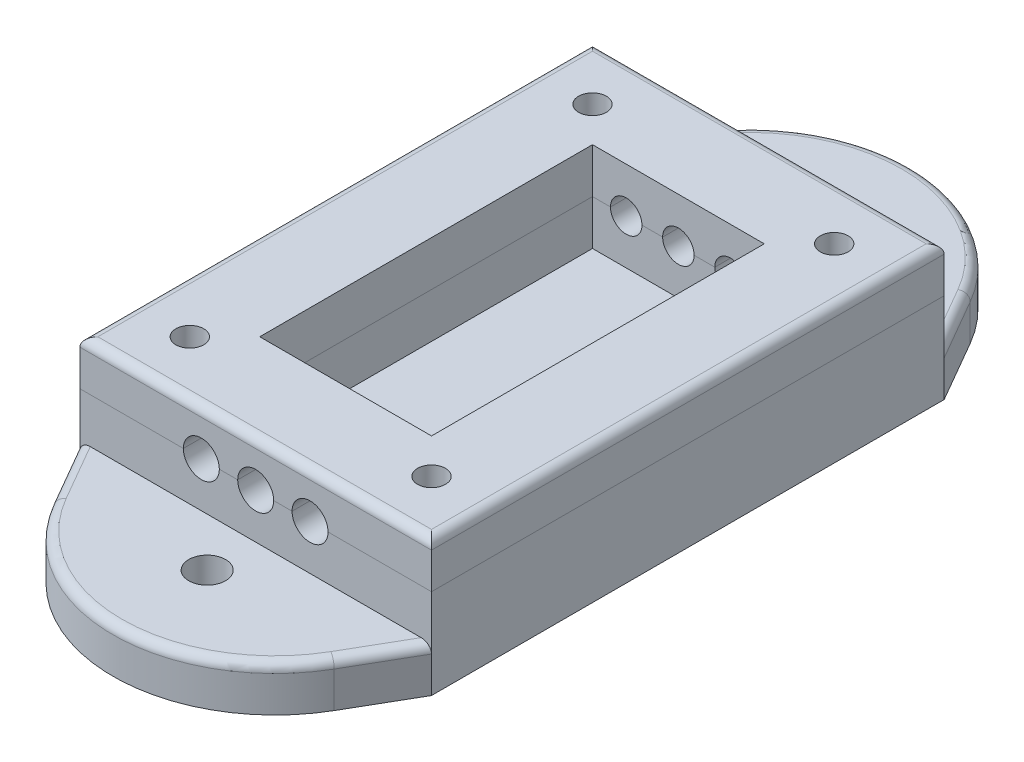
SolidWorks part; units mm, degrees
note: The reader was unsure of these and kept them because the rebuilt part matched: shared geometry of "Esquisse3<3>".
material "PLA"
ref_plane "Plan de face" through (0, 0, 0) normal (0, 0, 1) x (1, 0, 0)
ref_plane "Plan de dessus" through (0, 0, 0) normal (0, 1, 0) x (1, 0, 0)
ref_plane "Plan de droite" through (0, 0, 0) normal (1, 0, 0) x (0, 0, -1)
sketch "Esquisse1" plane through (0, 0, 0) normal (0, 0, 1) x (1, 0, 0)
  line L0 (0, 4) -> (0, 14.517) construction
  line L1 (-2.95, 10.1031) -> (2.95, 10.1031)
  line L22 (2.95, 10.1031) -> (2.95, 8.4831)
  line L23 (2.95, 8.4831) -> (5.71, 8.4831)
  line L24 (5.71, 8.4831) -> (5.71, 6.9831)
  line L25 (5.71, 6.9831) -> (3.5, 4.84)
  line L26 (3.5, 4.84) -> (-3.5, 4.84)
  line L27 (-5.71, 6.9831) -> (-3.5, 4.84)
  line L28 (-5.71, 8.4831) -> (-5.71, 6.9831)
  line L29 (-2.95, 8.4831) -> (-5.71, 8.4831)
  line L30 (-2.95, 10.1031) -> (-2.95, 8.4831)
  point P10 (0, 4.84)
  point P14 (0, 10.1031)
  point P41 (0, 0)
  point P46 (0, 0)
  line B0 (0, 0) -> (0, 4) construction
  line B1 (0, 4) -> (0.866, 4.5)
  line B2 (0, 4) -> (-0.866, 4.5)
  line B3 (0.866, 4.5) -> (3.4393, 4.5)
  line B4 (3.4393, 4.5) -> (6, 7.0607)
  line B5 (6, 7.0607) -> (6, 8.5)
  line B6 (6, 8.5) -> (3, 8.5)
  line B7 (3, 8.5) -> (3, 9.5)
  line B8 (3, 9.5) -> (3.5, 9.5)
  line B9 (3.5, 9.5) -> (3.5, 10)
  line B10 (3.5, 10) -> (8.5, 10)
  line B11 (0, 0) -> (1.2745, 0) construction
  line B12 (-3.5, -10) -> (-8.5, -10)
  line B13 (-3.4393, -4.5) -> (-6, -7.0607)
  line B14 (-3.5, 9.5) -> (-3.5, 10)
  line B15 (-3, 9.5) -> (-3.5, 9.5)
  line B16 (-3, 8.5) -> (-3, 9.5)
  line B17 (-6, 8.5) -> (-3, 8.5)
  line B18 (-6, 7.0607) -> (-6, 8.5)
  line B19 (-0.866, 4.5) -> (-3.4393, 4.5)
  line B20 (-3.4393, 4.5) -> (-6, 7.0607)
  line B21 (-3.5, 10) -> (-8.5, 10)
  line B22 (-0.866, -4.5) -> (-3.4393, -4.5)
  line B23 (-6, -7.0607) -> (-6, -8.5)
  line B24 (-6, -8.5) -> (-3, -8.5)
  line B25 (-3, -8.5) -> (-3, -9.5)
  line B26 (-3, -9.5) -> (-3.5, -9.5)
  line B27 (-3.5, -9.5) -> (-3.5, -10)
  line B28 (3.5, -10) -> (8.5, -10)
  line B29 (3.5, -9.5) -> (3.5, -10)
  line B30 (3, -9.5) -> (3.5, -9.5)
  line B31 (3, -8.5) -> (3, -9.5)
  line B32 (6, -8.5) -> (3, -8.5)
  line B33 (6, -7.0607) -> (6, -8.5)
  line B34 (3.4393, -4.5) -> (6, -7.0607)
  line B35 (0.866, -4.5) -> (3.4393, -4.5)
  line B36 (0, -4) -> (-0.866, -4.5)
  line B37 (0, -4) -> (0.866, -4.5)
  line B38 (10, -3.5) -> (10, -8.5)
  line B39 (9.5, -3.5) -> (10, -3.5)
  line B40 (8.5, -3) -> (9.5, -3)
  line B41 (9.5, -3) -> (9.5, -3.5)
  line B42 (8.5, -6) -> (8.5, -3)
  line B43 (7.0607, -6) -> (8.5, -6)
  line B44 (4.5, -3.4393) -> (7.0607, -6)
  line B45 (4.5, -0.866) -> (4.5, -3.4393)
  line B46 (4.5, 0.866) -> (4.5, 3.4393)
  line B47 (4.5, 3.4393) -> (7.0607, 6)
  line B48 (7.0607, 6) -> (8.5, 6)
  line B49 (8.5, 6) -> (8.5, 3)
  line B50 (8.5, 3) -> (9.5, 3)
  line B51 (9.5, 3) -> (9.5, 3.5)
  line B52 (9.5, 3.5) -> (10, 3.5)
  line B53 (10, 3.5) -> (10, 8.5)
  line B54 (-3.5, -9.5) -> (-3.5, -10)
  line B55 (-3, -8.5) -> (-3, -9.5)
  line B56 (-3, -9.5) -> (-3.5, -9.5)
  line B57 (-6, -8.5) -> (-3, -8.5)
  line B58 (-6, -7.0607) -> (-6, -8.5)
  line B59 (-3.4393, -4.5) -> (-6, -7.0607)
  line B60 (-0.866, -4.5) -> (-3.4393, -4.5)
  line B61 (0.866, -4.5) -> (3.4393, -4.5)
  line B62 (3.4393, -4.5) -> (6, -7.0607)
  line B63 (6, -7.0607) -> (6, -8.5)
  line B64 (6, -8.5) -> (3, -8.5)
  line B65 (3, -8.5) -> (3, -9.5)
  line B66 (3, -9.5) -> (3.5, -9.5)
  line B67 (3.5, -9.5) -> (3.5, -10)
  line B68 (-10, 3.5) -> (-10, 8.5)
  line B69 (-9.5, 3.5) -> (-10, 3.5)
  line B70 (-8.5, 3) -> (-9.5, 3)
  line B71 (-9.5, 3) -> (-9.5, 3.5)
  line B72 (-8.5, 6) -> (-8.5, 3)
  line B73 (-7.0607, 6) -> (-8.5, 6)
  line B74 (-4.5, 3.4393) -> (-7.0607, 6)
  line B75 (-4.5, 0.866) -> (-4.5, 3.4393)
  line B76 (-4.5, -0.866) -> (-4.5, -3.4393)
  line B77 (-4.5, -3.4393) -> (-7.0607, -6)
  line B78 (-7.0607, -6) -> (-8.5, -6)
  line B79 (-8.5, -6) -> (-8.5, -3)
  line B80 (-8.5, -3) -> (-9.5, -3)
  line B81 (-9.5, -3) -> (-9.5, -3.5)
  line B82 (-9.5, -3.5) -> (-10, -3.5)
  line B83 (-10, -3.5) -> (-10, -8.5)
  line B84 (4, 0) -> (4.5, -0.866)
  line B85 (4, 0) -> (4.5, 0.866)
  line B86 (0, -4) -> (-0.866, -4.5)
  line B87 (0, -4) -> (0.866, -4.5)
  line B88 (-4, 0) -> (-4.5, 0.866)
  line B89 (-4, 0) -> (-4.5, -0.866)
  line B90 (0, 0) -> (1.9445, 1.9445) construction
  arc B91 (8.5, 10) -> (10, 8.5) centre (8.5, 8.5) cw
  arc B92 (-8.5, 10) -> (-10, 8.5) centre (-8.5, 8.5) ccw
  arc B93 (-8.5, -10) -> (-10, -8.5) centre (-8.5, -8.5) cw
  arc B94 (8.5, -10) -> (10, -8.5) centre (8.5, -8.5) ccw
  circle B95 centre (0, 0) radius 2.75
  dimension "D1" = 2.95
  dimension "D2" = 1.62
  dimension "D3" = 2.76
  dimension "D4" = 1.5
  dimension "D5" = 135.88
  dimension "D6" = 3.5
  dimension "D7" = 0.34
sketch_block_instance "Bloc1-1"
sketch_block "Bloc1"
extrude "Boss.-Extru.1" add sketch "Esquisse1" against normal blind 20 contours L0 L26 L25 L24 L23 L22 L1 | L26 L0 L1 L30 L29 L28 L27
fillet "Congé1" radius 0.5 10 edges at (0, 4.84, -20) (-4.605, 5.9116, -20) (-5.71, 7.7331, -20) (4.605, 5.9116, -20) (5.71, 7.7331, -20) (-5.71, 7.7331, 0) (-4.605, 5.9116, 0) (0, 4.84, 0) (4.605, 5.9116, 0) (5.71, 7.7331, 0)
fillet "Congé2" radius 1 6 edges at (5.5636, 7.0451, -0.1464) (5.5636, 7.0451, -19.8536) (-5.5636, 7.0451, -0.1464) (-5.5636, 7.0451, -19.8536) (-5.71, 6.9831, -10) (5.71, 6.9831, -10)
sketch "Esquisse3" plane through (0, 10.1031, 0) normal (0, 1, 0) x (1, 0, 0)
  line L0 (0, 0) -> (0, 20) construction
  line L1 (-2.95, 20) -> (2.95, 20) construction
  line L2 (-9.55, -8.5) -> (-19.55, -18.5) construction
  line L3 (-19.55, 38.5) -> (19.55, 38.5)
  line L4 (-19.55, 38.5) -> (-19.55, -18.5)
  line L5 (-19.55, -18.5) -> (19.55, -18.5)
  line L6 (19.55, 38.5) -> (19.55, -18.5)
  line L7 (-19.55, 38.5) -> (19.55, -18.5) construction
  line L8 (-19.55, -18.5) -> (19.55, 38.5) construction
  line L9 (-9.55, 28.5) -> (9.55, 28.5)
  line L10 (-9.55, 28.5) -> (-9.55, -8.5)
  line L11 (-9.55, -8.5) -> (9.55, -8.5)
  line L12 (9.55, 28.5) -> (9.55, -8.5)
  line L13 (-9.55, 28.5) -> (9.55, -8.5) construction
  line L14 (-9.55, -8.5) -> (9.55, 28.5) construction
  line L15 (9.55, -8.5) -> (19.55, -18.5) construction
  line L16 (0, 10) -> (-5.1118, 10) construction
  circle A0 centre (-13.4391, -12.3891) radius 1.55
  circle A1 centre (13.4391, -12.3891) radius 1.55
  circle A2 centre (13.4391, 32.3891) radius 1.55
  circle A3 centre (-13.4391, 32.3891) radius 1.55
  point P5 (0, 10)
  point P10 (0, 10)
  dimension "D5" = 3.1
  dimension "D1" = 45
  dimension "D2" = 10
  dimension "D3" = 19.1
  dimension "D4" = 37
  dimension "D6" = 5.5
  dimension "D7" = 5.5
extrude "Boss.-Extru.2" add sketch "Esquisse3" along normal blind 5 contours A3 | A2 | L6 L3 L4 L5 A1 A0 L9 L12 L11 L10 A2 A3 | L12 L9 L10 L11 L2 A1 L0 A0 | A1 L2 A0 L0 | A0 | A1
extrude "Boss.-Extru.4" add sketch "Esquisse3<3>" along normal blind 15
sketch "Esquisse3<3>" plane through (0, 10.1031, 0) normal (0, 1, 0) x (1, 0, 0) same geometry as "Esquisse3"
sketch "Esquisse8" plane through (0, 0, -28.5) normal (0, 0, 1) x (1, 0, 0)
  line L0 (-9.55, 15.1031) -> (9.55, 15.1031) construction
  line L1 (9.55, 15.1031) -> (9.55, 25.1031) construction
  line L2 (9.55, 20.1031) -> (5.8, 20.1031) construction
  line L3 (5.8, 20.1031) -> (0, 20.1031) construction
  line L4 (0, 20.1031) -> (-5.8, 20.1031) construction
  circle A0 centre (5.8, 20.1031) radius 1.75
  circle A1 centre (0, 20.1031) radius 1.75
  circle A2 centre (-5.8, 20.1031) radius 1.75
  dimension "D2" = 3.5
  dimension "D4" = 3.5
  dimension "D6" = 3.5
  dimension "D1" = 3.75
  dimension "D3" = 5.8
  dimension "D5" = 5.8
extrude "Trous_moteur" cut sketch "Esquisse8" against normal up to next
sketch "Esquisse5" plane through (0, 0, 0) normal (0, 0, 1) x (1, 0, 0)
  line L0 (-5.21, 8.4831) -> (-5.71, 8.4831) construction
  line L1 (-3.5, 4.84) -> (-5.4062, 6.6885) construction
  line L2 (3.5, 4.84) -> (-3.5, 4.84) construction
  line L3 (5.4062, 6.6885) -> (3.5, 4.84) construction
  line L4 (5.71, 8.4831) -> (5.71, 7.4064) construction
  line L5 (5.71, 8.4831) -> (5.21, 8.4831) construction
  line L6 (2.95, 8.4831) -> (5.21, 8.4831) construction
  line L7 (-2.95, 8.4831) -> (-5.21, 8.4831) construction
  line L8 (-5.71, 7.4064) -> (-5.71, 8.4831) construction
  line L9 (-5.21, 8.4831) -> (-5.71, 8.4831)
  line L10 (-3.5, 4.84) -> (-5.4062, 6.6885)
  line L11 (3.5, 4.84) -> (-3.5, 4.84)
  line L12 (5.4062, 6.6885) -> (3.5, 4.84)
  line L13 (5.71, 8.4831) -> (5.71, 7.4064)
  line L14 (5.71, 8.4831) -> (5.21, 8.4831)
  line L15 (2.95, 8.4831) -> (5.21, 8.4831)
  line L16 (-2.95, 8.4831) -> (-5.21, 8.4831)
  line L17 (-5.71, 7.4064) -> (-5.71, 8.4831)
  line L18 (-2.95, 8.4831) -> (2.95, 8.4831)
  arc A0 (5.4062, 6.6885) -> (5.71, 7.4064) centre (4.71, 7.4064) ccw construction
  arc A1 (-5.71, 7.4064) -> (-5.4062, 6.6885) centre (-4.71, 7.4064) ccw construction
  arc A2 (5.4062, 6.6885) -> (5.71, 7.4064) centre (4.71, 7.4064) ccw
  arc A3 (-5.71, 7.4064) -> (-5.4062, 6.6885) centre (-4.71, 7.4064) ccw
extrude "Enlèv. mat.-Extru.1" cut sketch "Esquisse5" against normal through all
sketch "Esquisse9" plane through (0, 0, 8.5) normal (0, 0, -1) x (-1, 0, 0)
  line L0 (-9.55, 15.1031) -> (9.55, 15.1031) construction
  line L1 (9.55, 15.1031) -> (9.55, 25.1031) construction
  line L2 (9.55, 20.1031) -> (6.045, 20.1031) construction
  line L3 (-9.55, 15.1031) -> (-9.55, 25.1031) construction
  line L4 (-9.55, 20.1031) -> (-6.045, 20.1031) construction
  line L5 (-6.045, 20.1031) -> (6.045, 20.1031) construction
  circle A0 centre (6.045, 20.1031) radius 2
  circle A1 centre (-6.045, 20.1031) radius 2
  circle A2 centre (0, 20.1031) radius 2
  dimension "D2" = 4
  dimension "D4" = 4
  dimension "D5" = 4
  dimension "D1" = 12.09
extrude "Trous_cables_puissance" cut sketch "Esquisse9" against normal up to next
sketch "Esquisse12" plane through (0, 0, -20) normal (0, 0, -1) x (-1, 0, 0)
  line L4 (-2.95, 10.1031) -> (-2.95, 8.4831)
  line L5 (-2.95, 8.4831) -> (2.95, 8.4831)
  line L6 (2.95, 8.4831) -> (2.95, 10.1031)
  line L7 (2.95, 10.1031) -> (-2.95, 10.1031)
  line L8 (-2.95, 10.1031) -> (-2.95, 8.4831)
  line L9 (-2.95, 8.4831) -> (2.95, 8.4831)
  line L10 (2.95, 8.4831) -> (2.95, 10.1031)
  line L11 (2.95, 10.1031) -> (-2.95, 10.1031)
  dimension "D1" = 0
extrude "Enlèv. mat.-Extru.5" cut sketch "Esquisse12" against normal up to next contours L8 L9 L10 L11
sketch "Esquisse13" plane through (0, 10.1031, 0) normal (0, -1, 0) x (1, 0, 0)
  line L0 (-19.55, 18.5) -> (-15.5885, 25.3616)
  line L1 (15.5885, 25.3616) -> (19.55, 18.5)
  line L2 (-19.55, 18.5) -> (19.55, 18.5) construction
  line L3 (0, 44.3596) -> (0, 18.5) construction
  line L4 (-19.55, 18.5) -> (19.55, 18.5)
  circle A0 centre (0, 23.895) radius 2.05
  arc A1 (-15.5885, 25.3616) -> (15.5885, 25.3616) centre (0, 16.3616) cw
  dimension "D1" = 4.1
  dimension "D4" = 18
  dimension "D5" = 5.395
  dimension "D2" = 60
  dimension "D3" = 60
extrude "Boss.-Extru.5" add sketch "Esquisse13" against normal blind 5
ref_plane "Plan1" through (0, 0, -10) normal (0, 0, 1) x (1, 0, 0)
mirror "Symétrie1" about plane through (0, 0, -10) normal (0, 0, 1) of "Boss.-Extru.5"
fillet "Congé3" radius 1 10 edges at (17.5692, 15.1031, -41.9308) (-17.5692, 15.1031, -41.9308) (17.5692, 15.1031, 21.9308) (-17.5692, 15.1031, 21.9308) (0, 15.1031, -54.3616) (0, 25.1031, -38.5) (-19.55, 25.1031, -10) (0, 25.1031, 18.5) (19.55, 25.1031, -10) (0, 15.1031, 34.3616)
sketch "Esquisse14" plane through (0, 0, 18.5) normal (0, 0, 1) x (1, 0, 0)
  line L0 (-6.045, 20.1031) -> (0, 20.1031) construction
  line L1 (0, 20.1031) -> (19.55, 20.1031) construction
  line L2 (19.55, 24.1031) -> (19.55, 14.1031) construction
  line L3 (19.55, 20.1031) -> (-19.55, 20.1031)
  line L4 (-19.55, 24.1031) -> (-19.55, 14.1031) construction
  line L5 (-18.55, 25.1031) -> (18.55, 25.1031) construction
  line L6 (19.55, 24.1031) -> (19.55, 20.1031)
  line L7 (-19.55, 24.1031) -> (-19.55, 20.1031)
  line L8 (-18.55, 25.1031) -> (18.55, 25.1031)
  arc A0 (19.55, 24.1031) -> (18.55, 25.1031) centre (18.55, 24.1031) ccw construction
  arc A1 (-18.55, 25.1031) -> (-19.55, 24.1031) centre (-18.55, 24.1031) ccw construction
  arc A2 (19.55, 24.1031) -> (18.55, 25.1031) centre (18.55, 24.1031) ccw
  arc A3 (-18.55, 25.1031) -> (-19.55, 24.1031) centre (-18.55, 24.1031) ccw
split "Fractionner1" trim tools "Esquisse14" bodies to split 115 resulting bodies 116 117
equation "\"hole_thickness\"=15"
equation "\"D1@Boss.-Extru.4\"=\"hole_thickness\""
